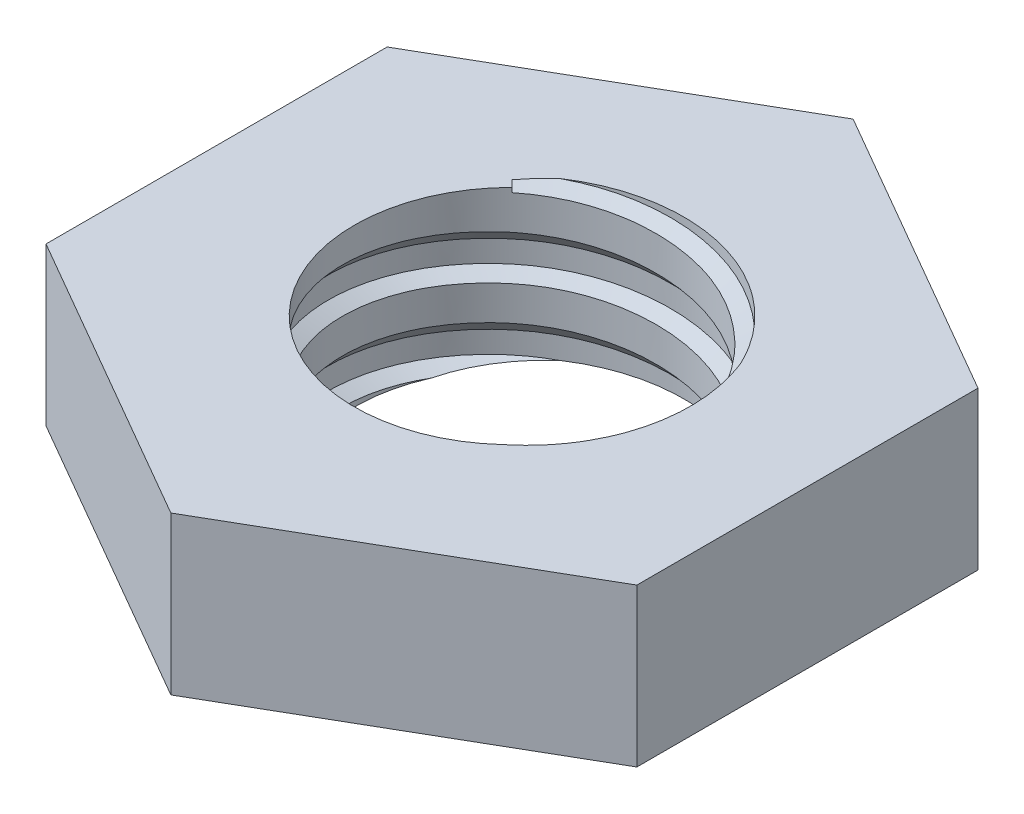
SolidWorks part; units mm, degrees
ref_plane "Front Plane" through (0, 0, 0) normal (0, 0, 1) x (1, 0, 0)
ref_plane "Top Plane" through (0, 0, 0) normal (0, 1, 0) x (1, 0, 0)
ref_plane "Right Plane" through (0, 0, 0) normal (1, 0, 0) x (0, 0, -1)
sketch "Sketch2" plane through (0, 0, 0) normal (0, 1, 0) x (1, 0, 0)
  line L7 (0, 8.6603) -> (-7.5, 4.3301)
  line L8 (-7.5, 4.3301) -> (-7.5, -4.3301)
  line L9 (-7.5, -4.3301) -> (0, -8.6603)
  line L10 (0, -8.6603) -> (7.5, -4.3301)
  line L11 (7.5, -4.3301) -> (7.5, 4.3301)
  line L12 (7.5, 4.3301) -> (0, 8.6603)
  circle A0 centre (0, 0) radius 7.5 construction
  dimension "D1" = 15
extrude "Boss-Extrude1" add sketch "Sketch2" along normal blind 4
sketch "Sketch3" plane through (0, 4, 0) normal (0, 1, 0) x (1, 0, 0)
  circle A0 centre (0, 0) radius 4
extrude "Cut-Extrude1" cut sketch "Sketch3" against normal blind 5
ref_plane "Plane1" through (0, 5, 0) normal (0, 1, 0) x (1, 0, 0)
sketch "Sketch4" plane through (0, 5, 0) normal (0, 1, 0) x (1, 0, 0)
  circle A0 centre (0, 0) radius 4
curve "Helix/Spiral1" pitch 2 height 121 turns 60.5
sketch "Sketch5" plane through (0, 0, 0) normal (0, 0, 1) x (1, 0, 0)
  line L4 (-3.9897, 3.2728) -> (-4.3608, 2.8624)
  line L5 (-4.3608, 2.8624) -> (-4.3608, 2.3098)
  line L6 (-4.3608, 2.3098) -> (-3.9897, 2.129)
  line L7 (-3.9897, 3.2728) -> (-3.9897, 2.129)
  spline S2 degree 3 poles (-2.8284, 5) (-2.4605, 4.9586) (-1.5695, 4.8749) (-0.0003, 4.75) (1.5707, 4.625) (2.902, 4.5) (3.7917, 4.375) (4.1041, 4.25) (3.7917, 4.125) (2.9021, 4) (1.1268, 3.8333) (-1.1268, 3.6667) (-2.9021, 3.5) (-3.7917, 3.375) (-4.1041, 3.25) (-3.7917, 3.125) (-2.9021, 3) (-1.1268, 2.8333) (1.1268, 2.6667) (2.9021, 2.5) (3.7917, 2.375) (4.1041, 2.25) (3.7917, 2.125) (2.9021, 2) (1.1268, 1.8333) (-1.1268, 1.6667) (-2.9021, 1.5) (-3.7917, 1.375) (-4.1041, 1.25) (-3.7917, 1.125) (-2.9021, 1) (-1.1268, 0.8333) (1.1268, 0.6667) (2.9021, 0.5) (3.7917, 0.375) (4.1041, 0.25) (3.7917, 0.125) (2.9021, 0) (1.1268, -0.1667) (-1.1268, -0.3333) (-2.9021, -0.5) (-3.7917, -0.625) (-4.1041, -0.75) (-3.7917, -0.875) (-2.9021, -1) (-1.1268, -1.1667) (1.1268, -1.3333) (2.9021, -1.5) (3.7917, -1.625) (4.1041, -1.75) (3.7917, -1.875) (2.9021, -2) (1.1268, -2.1667) (-1.1268, -2.3333) (-2.9021, -2.5) (-3.7917, -2.625) (-4.1041, -2.75) (-3.7917, -2.875) (-2.9021, -3) (-1.1268, -3.1667) (1.1268, -3.3333) (2.9021, -3.5) (3.7917, -3.625) (4.1041, -3.75) (3.7917, -3.875) (2.9021, -4) (1.1268, -4.1667) (-1.1268, -4.3333) (-2.9021, -4.5) (-3.7917, -4.625) (-4.1041, -4.75) (-3.7917, -4.875) (-2.9021, -5) (-1.1268, -5.1667) (1.1268, -5.3333) (2.9021, -5.5) (3.7917, -5.625) (4.1041, -5.75) (3.7917, -5.875) (2.9021, -6) (1.1268, -6.1667) (-1.1268, -6.3333) (-2.9021, -6.5) (-3.7917, -6.625) (-4.1041, -6.75) (-3.7917, -6.875) (-2.9021, -7) (-1.1268, -7.1667) (1.1268, -7.3333) (2.9021, -7.5) (3.7917, -7.625) (4.1041, -7.75) (3.7917, -7.875) (2.9021, -8) (1.1268, -8.1667) (-1.1268, -8.3333) (-2.9021, -8.5) (-3.7917, -8.625) (-4.1041, -8.75) (-3.7917, -8.875) (-2.9021, -9) (-1.1268, -9.1667) (1.1268, -9.3333) (2.9021, -9.5) (3.7917, -9.625) (4.1041, -9.75) (3.7917, -9.875) (2.9021, -10) (1.1268, -10.1667) (-1.1268, -10.3333) (-2.9021, -10.5) (-3.7917, -10.625) (-4.1041, -10.75) (-3.7917, -10.875) (-2.9021, -11) (-1.1268, -11.1667) (1.1268, -11.3333) (2.9021, -11.5) (3.7917, -11.625) (4.1041, -11.75) (3.7917, -11.875) (2.9021, -12) (1.1268, -12.1667) (-1.1268, -12.3333) (-2.9021, -12.5) (-3.7917, -12.625) (-4.1041, -12.75) (-3.7917, -12.875) (-2.9021, -13) (-1.1268, -13.1667) (1.1268, -13.3333) (2.9021, -13.5) (3.7917, -13.625) (4.1041, -13.75) (3.7917, -13.875) (2.9021, -14) (1.1268, -14.1667) (-1.1268, -14.3333) (-2.9021, -14.5) (-3.7917, -14.625) (-4.1041, -14.75) (-3.7917, -14.875) (-2.9021, -15) (-1.1268, -15.1667) (1.1268, -15.3333) (2.9021, -15.5) (3.7917, -15.625) (4.1041, -15.75) (3.7917, -15.875) (2.9021, -16) (1.1268, -16.1667) (-1.1268, -16.3333) (-2.9021, -16.5) (-3.7917, -16.625) (-4.1041, -16.75) (-3.7917, -16.875) (-2.9021, -17) (-1.1268, -17.1667) (1.1268, -17.3333) (2.9021, -17.5) (3.7917, -17.625) (4.1041, -17.75) (3.7917, -17.875) (2.9021, -18) (1.1268, -18.1667) (-1.1268, -18.3333) (-2.9021, -18.5) (-3.7917, -18.625) (-4.1041, -18.75) (-3.7917, -18.875) (-2.9021, -19) (-1.1268, -19.1667) (1.1268, -19.3333) (2.9021, -19.5) (3.7917, -19.625) (4.1041, -19.75) (3.7917, -19.875) (2.9021, -20) (1.1268, -20.1667) (-1.1268, -20.3333) (-2.9021, -20.5) (-3.7917, -20.625) (-4.1041, -20.75) (-3.7917, -20.875) (-2.9021, -21) (-1.1268, -21.1667) (1.1268, -21.3333) (2.9021, -21.5) (3.7917, -21.625) (4.1041, -21.75) (3.7917, -21.875) (2.9021, -22) (1.1268, -22.1667) (-1.1268, -22.3333) (-2.9021, -22.5) (-3.7917, -22.625) (-4.1041, -22.75) (-3.7917, -22.875) (-2.9021, -23) (-1.1268, -23.1667) (1.1268, -23.3333) (2.9021, -23.5) (3.7917, -23.625) (4.1041, -23.75) (3.7917, -23.875) (2.9021, -24) (1.1268, -24.1667) (-1.1268, -24.3333) (-2.9021, -24.5) (-3.7917, -24.625) (-4.1041, -24.75) (-3.7917, -24.875) (-2.9021, -25) (-1.1268, -25.1667) (1.1268, -25.3333) (2.9021, -25.5) (3.7917, -25.625) (4.1041, -25.75) (3.7917, -25.875) (2.9021, -26) (1.1268, -26.1667) (-1.1268, -26.3333) (-2.9021, -26.5) (-3.7917, -26.625) (-4.1041, -26.75) (-3.7917, -26.875) (-2.9021, -27) (-1.1268, -27.1667) (1.1268, -27.3333) (2.9021, -27.5) (3.7917, -27.625) (4.1041, -27.75) (3.7917, -27.875) (2.9021, -28) (1.1268, -28.1667) (-1.1268, -28.3333) (-2.9021, -28.5) (-3.7917, -28.625) (-4.1041, -28.75) (-3.7917, -28.875) (-2.9021, -29) (-1.1268, -29.1667) (1.1268, -29.3333) (2.9021, -29.5) (3.7917, -29.625) (4.1041, -29.75) (3.7917, -29.875) (2.9021, -30) (1.1268, -30.1667) (-1.1268, -30.3333) (-2.9021, -30.5) (-3.7917, -30.625) (-4.1041, -30.75) (-3.7917, -30.875) (-2.9021, -31) (-1.1268, -31.1667) (1.1268, -31.3333) (2.9021, -31.5) (3.7917, -31.625) (4.1041, -31.75) (3.7917, -31.875) (2.9021, -32) (1.1268, -32.1667) (-1.1268, -32.3333) (-2.9021, -32.5) (-3.7917, -32.625) (-4.1041, -32.75) (-3.7917, -32.875) (-2.9021, -33) (-1.1268, -33.1667) (1.1268, -33.3333) (2.9021, -33.5) (3.7917, -33.625) (4.1041, -33.75) (3.7917, -33.875) (2.9021, -34) (1.1268, -34.1667) (-1.1268, -34.3333) (-2.9021, -34.5) (-3.7917, -34.625) (-4.1041, -34.75) (-3.7917, -34.875) (-2.9021, -35) (-1.1268, -35.1667) (1.1268, -35.3333) (2.9021, -35.5) (3.7917, -35.625) (4.1041, -35.75) (3.7917, -35.875) (2.9021, -36) (1.1268, -36.1667) (-1.1268, -36.3333) (-2.9021, -36.5) (-3.7917, -36.625) (-4.1041, -36.75) (-3.7917, -36.875) (-2.9021, -37) (-1.1268, -37.1667) (1.1268, -37.3333) (2.9021, -37.5) (3.7917, -37.625) (4.1041, -37.75) (3.7917, -37.875) (2.9021, -38) (1.1268, -38.1667) (-1.1268, -38.3333) (-2.9021, -38.5) (-3.7917, -38.625) (-4.1041, -38.75) (-3.7917, -38.875) (-2.9021, -39) (-1.1268, -39.1667) (1.1268, -39.3333) (2.9021, -39.5) (3.7917, -39.625) (4.1041, -39.75) (3.7917, -39.875) (2.9021, -40) (1.1268, -40.1667) (-1.1268, -40.3333) (-2.9021, -40.5) (-3.7917, -40.625) (-4.1041, -40.75) (-3.7917, -40.875) (-2.9021, -41) (-1.1268, -41.1667) (1.1268, -41.3333) (2.9021, -41.5) (3.7917, -41.625) (4.1041, -41.75) (3.7917, -41.875) (2.9021, -42) (1.1268, -42.1667) (-1.1268, -42.3333) (-2.9021, -42.5) (-3.7917, -42.625) (-4.1041, -42.75) (-3.7917, -42.875) (-2.9021, -43) (-1.1268, -43.1667) (1.1268, -43.3333) (2.9021, -43.5) (3.7917, -43.625) (4.1041, -43.75) (3.7917, -43.875) (2.9021, -44) (1.1268, -44.1667) (-1.1268, -44.3333) (-2.9021, -44.5) (-3.7917, -44.625) (-4.1041, -44.75) (-3.7917, -44.875) (-2.9021, -45) (-1.1268, -45.1667) (1.1268, -45.3333) (2.9021, -45.5) (3.7917, -45.625) (4.1041, -45.75) (3.7917, -45.875) (2.9021, -46) (1.1268, -46.1667) (-1.1268, -46.3333) (-2.9021, -46.5) (-3.7917, -46.625) (-4.1041, -46.75) (-3.7917, -46.875) (-2.9021, -47) (-1.1268, -47.1667) (1.1268, -47.3333) (2.9021, -47.5) (3.7917, -47.625) (4.1041, -47.75) (3.7917, -47.875) (2.9021, -48) (1.1268, -48.1667) (-1.1268, -48.3333) (-2.9021, -48.5) (-3.7917, -48.625) (-4.1041, -48.75) (-3.7917, -48.875) (-2.9021, -49) (-1.1268, -49.1667) (1.1268, -49.3333) (2.9021, -49.5) (3.7917, -49.625) (4.1041, -49.75) (3.7917, -49.875) (2.9021, -50) (1.1268, -50.1667) (-1.1268, -50.3333) (-2.9021, -50.5) (-3.7917, -50.625) (-4.1041, -50.75) (-3.7917, -50.875) (-2.9021, -51) (-1.1268, -51.1667) (1.1268, -51.3333) (2.9021, -51.5) (3.7917, -51.625) (4.1041, -51.75) (3.7917, -51.875) (2.9021, -52) (1.1268, -52.1667) (-1.1268, -52.3333) (-2.9021, -52.5) (-3.7917, -52.625) (-4.1041, -52.75) (-3.7917, -52.875) (-2.9021, -53) (-1.1268, -53.1667) (1.1268, -53.3333) (2.9021, -53.5) (3.7917, -53.625) (4.1041, -53.75) (3.7917, -53.875) (2.9021, -54) (1.1268, -54.1667) (-1.1268, -54.3333) (-2.9021, -54.5) (-3.7917, -54.625) (-4.1041, -54.75) (-3.7917, -54.875) (-2.9021, -55) (-1.1268, -55.1667) (1.1268, -55.3333) (2.9021, -55.5) (3.7917, -55.625) (4.1041, -55.75) (3.7917, -55.875) (2.9021, -56) (1.1268, -56.1667) (-1.1268, -56.3333) (-2.9021, -56.5) (-3.7917, -56.625) (-4.1041, -56.75) (-3.7917, -56.875) (-2.9021, -57) (-1.1268, -57.1667) (1.1268, -57.3333) (2.9021, -57.5) (3.7917, -57.625) (4.1041, -57.75) (3.7917, -57.875) (2.9021, -58) (1.1268, -58.1667) (-1.1268, -58.3333) (-2.9021, -58.5) (-3.7917, -58.625) (-4.1041, -58.75) (-3.7917, -58.875) (-2.9021, -59) (-1.1268, -59.1667) (1.1268, -59.3333) (2.9021, -59.5) (3.7917, -59.625) (4.1041, -59.75) (3.7917, -59.875) (2.9021, -60) (1.1268, -60.1667) (-1.1268, -60.3333) (-2.9021, -60.5) (-3.7917, -60.625) (-4.1041, -60.75) (-3.7917, -60.875) (-2.9021, -61) (-1.1268, -61.1667) (1.1268, -61.3333) (2.9021, -61.5) (3.7917, -61.625) (4.1041, -61.75) (3.7917, -61.875) (2.9021, -62) (1.1268, -62.1667) (-1.1268, -62.3333) (-2.9021, -62.5) (-3.7917, -62.625) (-4.1041, -62.75) (-3.7917, -62.875) (-2.9021, -63) (-1.1268, -63.1667) (1.1268, -63.3333) (2.9021, -63.5) (3.7917, -63.625) (4.1041, -63.75) (3.7917, -63.875) (2.9021, -64) (1.1268, -64.1667) (-1.1268, -64.3333) (-2.9021, -64.5) (-3.7917, -64.625) (-4.1041, -64.75) (-3.7917, -64.875) (-2.9021, -65) (-1.1268, -65.1667) (1.1268, -65.3333) (2.9021, -65.5) (3.7917, -65.625) (4.1041, -65.75) (3.7917, -65.875) (2.9021, -66) (1.1268, -66.1667) (-1.1268, -66.3333) (-2.9021, -66.5) (-3.7917, -66.625) (-4.1041, -66.75) (-3.7917, -66.875) (-2.9021, -67) (-1.1268, -67.1667) (1.1268, -67.3333) (2.9021, -67.5) (3.7917, -67.625) (4.1041, -67.75) (3.7917, -67.875) (2.9021, -68) (1.1268, -68.1667) (-1.1268, -68.3333) (-2.9021, -68.5) (-3.7917, -68.625) (-4.1041, -68.75) (-3.7917, -68.875) (-2.9021, -69) (-1.1268, -69.1667) (1.1268, -69.3333) (2.9021, -69.5) (3.7917, -69.625) (4.1041, -69.75) (3.7917, -69.875) (2.9021, -70) (1.1268, -70.1667) (-1.1268, -70.3333) (-2.9021, -70.5) (-3.7917, -70.625) (-4.1041, -70.75) (-3.7917, -70.875) (-2.9021, -71) (-1.1268, -71.1667) (1.1268, -71.3333) (2.9021, -71.5) (3.7917, -71.625) (4.1041, -71.75) (3.7917, -71.875) (2.9021, -72) (1.1268, -72.1667) (-1.1268, -72.3333) (-2.9021, -72.5) (-3.7917, -72.625) (-4.1041, -72.75) (-3.7917, -72.875) (-2.9021, -73) (-1.1268, -73.1667) (1.1268, -73.3333) (2.9021, -73.5) (3.7917, -73.625) (4.1041, -73.75) (3.7917, -73.875) (2.9021, -74) (1.1268, -74.1667) (-1.1268, -74.3333) (-2.9021, -74.5) (-3.7917, -74.625) (-4.1041, -74.75) (-3.7917, -74.875) (-2.9021, -75) (-1.1268, -75.1667) (1.1268, -75.3333) (2.9021, -75.5) (3.7917, -75.625) (4.1041, -75.75) (3.7917, -75.875) (2.9021, -76) (1.1268, -76.1667) (-1.1268, -76.3333) (-2.9021, -76.5) (-3.7917, -76.625) (-4.1041, -76.75) (-3.7917, -76.875) (-2.9021, -77) (-1.1268, -77.1667) (1.1268, -77.3333) (2.9021, -77.5) (3.7917, -77.625) (4.1041, -77.75) (3.7917, -77.875) (2.9021, -78) (1.1268, -78.1667) (-1.1268, -78.3333) (-2.9021, -78.5) (-3.7917, -78.625) (-4.1041, -78.75) (-3.7917, -78.875) (-2.9021, -79) (-1.1268, -79.1667) (1.1268, -79.3333) (2.9021, -79.5) (3.7917, -79.625) (4.1041, -79.75) (3.7917, -79.875) (2.9021, -80) (1.1268, -80.1667) (-1.1268, -80.3333) (-2.9021, -80.5) (-3.7917, -80.625) (-4.1041, -80.75) (-3.7917, -80.875) (-2.9021, -81) (-1.1268, -81.1667) (1.1268, -81.3333) (2.9021, -81.5) (3.7917, -81.625) (4.1041, -81.75) (3.7917, -81.875) (2.9021, -82) (1.1268, -82.1667) (-1.1268, -82.3333) (-2.9021, -82.5) (-3.7917, -82.625) (-4.1041, -82.75) (-3.7917, -82.875) (-2.9021, -83) (-1.1268, -83.1667) (1.1268, -83.3333) (2.9021, -83.5) (3.7917, -83.625) (4.1041, -83.75) (3.7917, -83.875) (2.9021, -84) (1.1268, -84.1667) (-1.1268, -84.3333) (-2.9021, -84.5) (-3.7917, -84.625) (-4.1041, -84.75) (-3.7917, -84.875) (-2.9021, -85) (-1.1268, -85.1667) (1.1268, -85.3333) (2.9021, -85.5) (3.7917, -85.625) (4.1041, -85.75) (3.7917, -85.875) (2.9021, -86) (1.1268, -86.1667) (-1.1268, -86.3333) (-2.9021, -86.5) (-3.7917, -86.625) (-4.1041, -86.75) (-3.7917, -86.875) (-2.9021, -87) (-1.1268, -87.1667) (1.1268, -87.3333) (2.9021, -87.5) (3.7917, -87.625) (4.1041, -87.75) (3.7917, -87.875) (2.9021, -88) (1.1268, -88.1667) (-1.1268, -88.3333) (-2.9021, -88.5) (-3.7917, -88.625) (-4.1041, -88.75) (-3.7917, -88.875) (-2.9021, -89) (-1.1268, -89.1667) (1.1268, -89.3333) (2.9021, -89.5) (3.7917, -89.625) (4.1041, -89.75) (3.7917, -89.875) (2.9021, -90) (1.1268, -90.1667) (-1.1268, -90.3333) (-2.9021, -90.5) (-3.7917, -90.625) (-4.1041, -90.75) (-3.7917, -90.875) (-2.9021, -91) (-1.1268, -91.1667) (1.1268, -91.3333) (2.9021, -91.5) (3.7917, -91.625) (4.1041, -91.75) (3.7917, -91.875) (2.9021, -92) (1.1268, -92.1667) (-1.1268, -92.3333) (-2.9021, -92.5) (-3.7917, -92.625) (-4.1041, -92.75) (-3.7917, -92.875) (-2.9021, -93) (-1.1268, -93.1667) (1.1268, -93.3333) (2.9021, -93.5) (3.7917, -93.625) (4.1041, -93.75) (3.7917, -93.875) (2.9021, -94) (1.1268, -94.1667) (-1.1268, -94.3333) (-2.9021, -94.5) (-3.7917, -94.625) (-4.1041, -94.75) (-3.7917, -94.875) (-2.9021, -95) (-1.1268, -95.1667) (1.1268, -95.3333) (2.9021, -95.5) (3.7917, -95.625) (4.1041, -95.75) (3.7917, -95.875) (2.9021, -96) (1.1268, -96.1667) (-1.1268, -96.3333) (-2.9021, -96.5) (-3.7917, -96.625) (-4.1041, -96.75) (-3.7917, -96.875) (-2.9021, -97) (-1.1268, -97.1667) (1.1268, -97.3333) (2.9021, -97.5) (3.7917, -97.625) (4.1041, -97.75) (3.7917, -97.875) (2.9021, -98) (1.1268, -98.1667) (-1.1268, -98.3333) (-2.9021, -98.5) (-3.7917, -98.625) (-4.1041, -98.75) (-3.7917, -98.875) (-2.9021, -99) (-1.1268, -99.1667) (1.1268, -99.3333) (2.9021, -99.5) (3.7917, -99.625) (4.1041, -99.75) (3.7917, -99.875) (2.9021, -100) (1.1268, -100.1667) (-1.1268, -100.3333) (-2.9021, -100.5) (-3.7917, -100.625) (-4.1041, -100.75) (-3.7917, -100.875) (-2.9021, -101) (-1.1268, -101.1667) (1.1268, -101.3333) (2.9021, -101.5) (3.7917, -101.625) (4.1041, -101.75) (3.7917, -101.875) (2.9021, -102) (1.1268, -102.1667) (-1.1268, -102.3333) (-2.9021, -102.5) (-3.7917, -102.625) (-4.1041, -102.75) (-3.7917, -102.875) (-2.9021, -103) (-1.1268, -103.1667) (1.1268, -103.3333) (2.9021, -103.5) (3.7917, -103.625) (4.1041, -103.75) (3.7917, -103.875) (2.9021, -104) (1.1268, -104.1667) (-1.1268, -104.3333) (-2.9021, -104.5) (-3.7917, -104.625) (-4.1041, -104.75) (-3.7917, -104.875) (-2.9021, -105) (-1.1268, -105.1667) (1.1268, -105.3333) (2.9021, -105.5) (3.7917, -105.625) (4.1041, -105.75) (3.7917, -105.875) (2.9021, -106) (1.1268, -106.1667) (-1.1268, -106.3333) (-2.9021, -106.5) (-3.7917, -106.625) (-4.1041, -106.75) (-3.7917, -106.875) (-2.9021, -107) (-1.1268, -107.1667) (1.1268, -107.3333) (2.9021, -107.5) (3.7917, -107.625) (4.1041, -107.75) (3.7917, -107.875) (2.9021, -108) (1.1268, -108.1667) (-1.1268, -108.3333) (-2.9021, -108.5) (-3.7917, -108.625) (-4.1041, -108.75) (-3.7917, -108.875) (-2.9021, -109) (-1.1268, -109.1667) (1.1268, -109.3333) (2.9021, -109.5) (3.7917, -109.625) (4.1041, -109.75) (3.7917, -109.875) (2.9021, -110) (1.1268, -110.1667) (-1.1268, -110.3333) (-2.9021, -110.5) (-3.7917, -110.625) (-4.1041, -110.75) (-3.7917, -110.875) (-2.9021, -111) (-1.1268, -111.1667) (1.1268, -111.3333) (2.9021, -111.5) (3.7917, -111.625) (4.1041, -111.75) (3.7917, -111.875) (2.9021, -112) (1.1268, -112.1667) (-1.1268, -112.3333) (-2.9021, -112.5) (-3.7917, -112.625) (-4.1041, -112.75) (-3.7917, -112.875) (-2.9021, -113) (-1.1268, -113.1667) (1.1268, -113.3333) (2.9021, -113.5) (3.7917, -113.625) (4.1041, -113.75) (3.7917, -113.875) (2.9021, -114) (1.1268, -114.1667) (-1.1268, -114.3333) (-2.9021, -114.5) (-3.7917, -114.625) (-4.1041, -114.75) (-3.7917, -114.875) (-2.9021, -115) (-1.5706, -115.125) (0, -115.25) (1.5706, -115.375) (2.902, -115.5) (3.7918, -115.625) (4.1038, -115.75) (3.7928, -115.8749) (3.1963, -115.9586) (2.8284, -116) knots 0 0 0 0 0.001033 0.002066 0.003099 0.004132 0.005165 0.006198 0.007231 0.008264 0.009298 0.011364 0.012397 0.01343 0.014463 0.015496 0.016529 0.017562 0.019628 0.020661 0.021694 0.022727 0.02376 0.024793 0.025826 0.027893 0.028926 0.029959 0.030992 0.032025 0.033058 0.034091 0.036157 0.03719 0.038223 0.039256 0.040289 0.041322 0.042355 0.044421 0.045455 0.046488 0.047521 0.048554 0.049587 0.05062 0.052686 0.053719 0.054752 0.055785 0.056818 0.057851 0.058884 0.06095 0.061983 0.063017 0.06405 0.065083 0.066116 0.067149 0.069215 0.070248 0.071281 0.072314 0.073347 0.07438 0.075413 0.077479 0.078512 0.079545 0.080579 0.081612 0.082645 0.083678 0.085744 0.086777 0.08781 0.088843 0.089876 0.090909 0.091942 0.094008 0.095041 0.096074 0.097107 0.09814 0.099174 0.100207 0.102273 0.103306 0.104339 0.105372 0.106405 0.107438 0.108471 0.110537 0.11157 0.112603 0.113636 0.114669 0.115702 0.116736 0.118802 0.119835 0.120868 0.121901 0.122934 0.123967 0.125 0.127066 0.128099 0.129132 0.130165 0.131198 0.132231 0.133264 0.135331 0.136364 0.137397 0.13843 0.139463 0.140496 0.141529 0.143595 0.144628 0.145661 0.146694 0.147727 0.14876 0.149793 0.15186 0.152893 0.153926 0.154959 0.155992 0.157025 0.158058 0.160124 0.161157 0.16219 0.163223 0.164256 0.165289 0.166322 0.168388 0.169421 0.170455 0.171488 0.172521 0.173554 0.174587 0.176653 0.177686 0.178719 0.179752 0.180785 0.181818 0.182851 0.184917 0.18595 0.186983 0.188017 0.18905 0.190083 0.191116 0.193182 0.194215 0.195248 0.196281 0.197314 0.198347 0.19938 0.201446 0.202479 0.203512 0.204545 0.205579 0.206612 0.207645 0.209711 0.210744 0.211777 0.21281 0.213843 0.214876 0.215909 0.217975 0.219008 0.220041 0.221074 0.222107 0.22314 0.224174 0.22624 0.227273 0.228306 0.229339 0.230372 0.231405 0.232438 0.234504 0.235537 0.23657 0.237603 0.238636 0.239669 0.240702 0.242769 0.243802 0.244835 0.245868 0.246901 0.247934 0.248967 0.251033 0.252066 0.253099 0.254132 0.255165 0.256198 0.257231 0.259298 0.260331 0.261364 0.262397 0.26343 0.264463 0.265496 0.267562 0.268595 0.269628 0.270661 0.271694 0.272727 0.27376 0.275826 0.27686 0.277893 0.278926 0.279959 0.280992 0.282025 0.284091 0.285124 0.286157 0.28719 0.288223 0.289256 0.290289 0.292355 0.293388 0.294421 0.295455 0.296488 0.297521 0.298554 0.30062 0.301653 0.302686 0.303719 0.304752 0.305785 0.306818 0.308884 0.309917 0.31095 0.311983 0.313017 0.31405 0.315083 0.317149 0.318182 0.319215 0.320248 0.321281 0.322314 0.323347 0.325413 0.326446 0.327479 0.328512 0.329545 0.330579 0.331612 0.333678 0.334711 0.335744 0.336777 0.33781 0.338843 0.339876 0.341942 0.342975 0.344008 0.345041 0.346074 0.347107 0.34814 0.350207 0.35124 0.352273 0.353306 0.354339 0.355372 0.356405 0.358471 0.359504 0.360537 0.36157 0.362603 0.363636 0.364669 0.366736 0.367769 0.368802 0.369835 0.370868 0.371901 0.372934 0.375 0.376033 0.377066 0.378099 0.379132 0.380165 0.381198 0.383264 0.384298 0.385331 0.386364 0.387397 0.38843 0.389463 0.391529 0.392562 0.393595 0.394628 0.395661 0.396694 0.397727 0.399793 0.400826 0.40186 0.402893 0.403926 0.404959 0.405992 0.408058 0.409091 0.410124 0.411157 0.41219 0.413223 0.414256 0.416322 0.417355 0.418388 0.419421 0.420455 0.421488 0.422521 0.424587 0.42562 0.426653 0.427686 0.428719 0.429752 0.430785 0.432851 0.433884 0.434917 0.43595 0.436983 0.438017 0.43905 0.441116 0.442149 0.443182 0.444215 0.445248 0.446281 0.447314 0.44938 0.450413 0.451446 0.452479 0.453512 0.454545 0.455579 0.457645 0.458678 0.459711 0.460744 0.461777 0.46281 0.463843 0.465909 0.466942 0.467975 0.469008 0.470041 0.471074 0.472107 0.474174 0.475207 0.47624 0.477273 0.478306 0.479339 0.480372 0.482438 0.483471 0.484504 0.485537 0.48657 0.487603 0.488636 0.490702 0.491736 0.492769 0.493802 0.494835 0.495868 0.496901 0.498967 0.5 0.501033 0.502066 0.503099 0.504132 0.505165 0.507231 0.508264 0.509298 0.510331 0.511364 0.512397 0.51343 0.515496 0.516529 0.517562 0.518595 0.519628 0.520661 0.521694 0.52376 0.524793 0.525826 0.52686 0.527893 0.528926 0.529959 0.532025 0.533058 0.534091 0.535124 0.536157 0.53719 0.538223 0.540289 0.541322 0.542355 0.543388 0.544421 0.545455 0.546488 0.548554 0.549587 0.55062 0.551653 0.552686 0.553719 0.554752 0.556818 0.557851 0.558884 0.559917 0.56095 0.561983 0.563017 0.565083 0.566116 0.567149 0.568182 0.569215 0.570248 0.571281 0.573347 0.57438 0.575413 0.576446 0.577479 0.578512 0.579545 0.581612 0.582645 0.583678 0.584711 0.585744 0.586777 0.58781 0.589876 0.590909 0.591942 0.592975 0.594008 0.595041 0.596074 0.59814 0.599174 0.600207 0.60124 0.602273 0.603306 0.604339 0.606405 0.607438 0.608471 0.609504 0.610537 0.61157 0.612603 0.614669 0.615702 0.616736 0.617769 0.618802 0.619835 0.620868 0.622934 0.623967 0.625 0.626033 0.627066 0.628099 0.629132 0.631198 0.632231 0.633264 0.634298 0.635331 0.636364 0.637397 0.639463 0.640496 0.641529 0.642562 0.643595 0.644628 0.645661 0.647727 0.64876 0.649793 0.650826 0.65186 0.652893 0.653926 0.655992 0.657025 0.658058 0.659091 0.660124 0.661157 0.66219 0.664256 0.665289 0.666322 0.667355 0.668388 0.669421 0.670455 0.672521 0.673554 0.674587 0.67562 0.676653 0.677686 0.678719 0.680785 0.681818 0.682851 0.683884 0.684917 0.68595 0.686983 0.68905 0.690083 0.691116 0.692149 0.693182 0.694215 0.695248 0.697314 0.698347 0.69938 0.700413 0.701446 0.702479 0.703512 0.705579 0.706612 0.707645 0.708678 0.709711 0.710744 0.711777 0.713843 0.714876 0.715909 0.716942 0.717975 0.719008 0.720041 0.722107 0.72314 0.724174 0.725207 0.72624 0.727273 0.728306 0.730372 0.731405 0.732438 0.733471 0.734504 0.735537 0.73657 0.738636 0.739669 0.740702 0.741736 0.742769 0.743802 0.744835 0.746901 0.747934 0.748967 0.75 0.751033 0.752066 0.753099 0.755165 0.756198 0.757231 0.758264 0.759298 0.760331 0.761364 0.76343 0.764463 0.765496 0.766529 0.767562 0.768595 0.769628 0.771694 0.772727 0.77376 0.774793 0.775826 0.77686 0.777893 0.779959 0.780992 0.782025 0.783058 0.784091 0.785124 0.786157 0.788223 0.789256 0.790289 0.791322 0.792355 0.793388 0.794421 0.796488 0.797521 0.798554 0.799587 0.80062 0.801653 0.802686 0.804752 0.805785 0.806818 0.807851 0.808884 0.809917 0.81095 0.813017 0.81405 0.815083 0.816116 0.817149 0.818182 0.819215 0.821281 0.822314 0.823347 0.82438 0.825413 0.826446 0.827479 0.829545 0.830579 0.831612 0.832645 0.833678 0.834711 0.835744 0.83781 0.838843 0.839876 0.840909 0.841942 0.842975 0.844008 0.846074 0.847107 0.84814 0.849174 0.850207 0.85124 0.852273 0.854339 0.855372 0.856405 0.857438 0.858471 0.859504 0.860537 0.862603 0.863636 0.864669 0.865702 0.866736 0.867769 0.868802 0.870868 0.871901 0.872934 0.873967 0.875 0.876033 0.877066 0.879132 0.880165 0.881198 0.882231 0.883264 0.884298 0.885331 0.887397 0.88843 0.889463 0.890496 0.891529 0.892562 0.893595 0.895661 0.896694 0.897727 0.89876 0.899793 0.900826 0.90186 0.903926 0.904959 0.905992 0.907025 0.908058 0.909091 0.910124 0.91219 0.913223 0.914256 0.915289 0.916322 0.917355 0.918388 0.920455 0.921488 0.922521 0.923554 0.924587 0.92562 0.926653 0.928719 0.929752 0.930785 0.931818 0.932851 0.933884 0.934917 0.936983 0.938017 0.93905 0.940083 0.941116 0.942149 0.943182 0.945248 0.946281 0.947314 0.948347 0.94938 0.950413 0.951446 0.953512 0.954545 0.955579 0.956612 0.957645 0.958678 0.959711 0.961777 0.96281 0.963843 0.964876 0.965909 0.966942 0.967975 0.970041 0.971074 0.972107 0.97314 0.974174 0.975207 0.97624 0.978306 0.979339 0.980372 0.981405 0.982438 0.983471 0.984504 0.98657 0.987603 0.988636 0.989669 0.990702 0.991736 0.992769 0.993802 0.994835 0.995868 0.996901 0.997934 0.998967 1 1 1 1 construction
sweep "Cut-Sweep2" cut profiles "Sketch5" path "Helix/Spiral1" align with end faces yes
